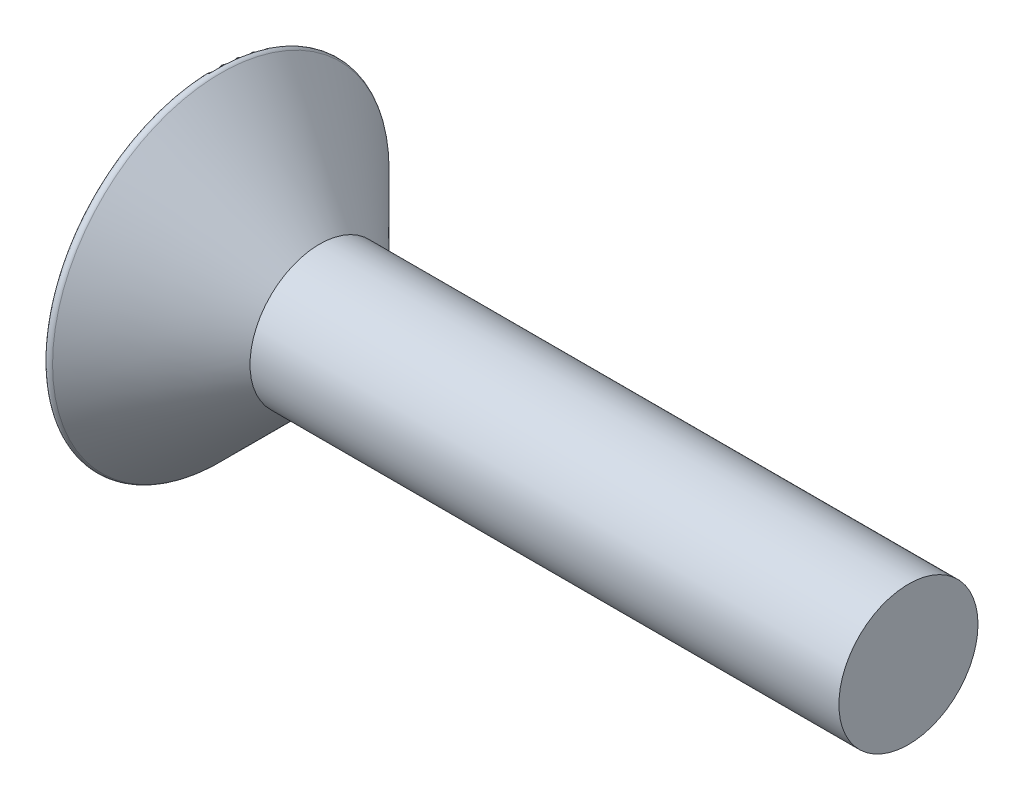
SolidWorks part; units mm, degrees
ref_plane "Front" through (0, 0, 0) normal (0, 0, 1) x (1, 0, 0)
ref_plane "Top" through (0, 0, 0) normal (0, 1, 0) x (1, 0, 0)
ref_plane "Right" through (0, 0, 0) normal (1, 0, 0) x (0, 0, -1)
ref_plane "Plane1" through (4.6, 0, 0) normal (1, 0, 0) x (0, 0, -1)
sketch "Sketch1" plane through (4.6, 0, 0) normal (1, 0, 0) x (0, 0, -1)
  circle A0 centre (0, 0) radius 3
  dimension "d" = 6
extrude "BaseHead" add sketch "Sketch1" against normal blind 4.6 draft 45 draft outward yes
sketch "Sketch2" plane through (4.6, 0, 0) normal (1, 0, 0) x (0, 0, -1)
  circle A1 centre (0, 0) radius 3
  dimension "d" = 6
extrude "BaseBody" add sketch "Sketch2" along normal blind 30
cosmetic thread "ThreadCosmetic1" [suppressed] parameters "bb"=23.4, "THD_MINOR"=5
sketch "Sketch7" plane through (0, 0, 0) normal (0, 0, 1) x (1, 0, 0)
  line L0 (30, 6) -> (30, -6)
  line L1 (34.6, -3) -> (34.6, 3) construction
  line L2 (34.6, 3) -> (4.6, 3) construction
  line L3 (4.6, -3) -> (34.6, -3) construction
  dimension "D1" = 4.6
  dimension "D2" = 3
  dimension "D3" = 3
extrude "Cut-Extrude3" cut sketch "Sketch7" against normal through all and the other way through all
sketch "Sketch8" plane through (0, 0, 0) normal (0, 0, 1) x (1, 0, 0)
  line L0 (0, 7.6) -> (4.6, 3)
  line L2 (6.3071, 2.7071) -> (6.6, 3)
  line L3 (6.6, 3) -> (6.6, 7.6)
  line L4 (6.6, 7.6) -> (0, 7.6)
  line L5 (30, 3) -> (4.6, 3) construction
  line L6 (0, 0) -> (8.9995, 0) construction
  line L7 (4.6, 3) -> (4.6, -3) construction
  arc A0 (4.6, 3) -> (6.3071, 2.7071) centre (5.6607, 4.0607) ccw
  dimension "r" = 1.5
  dimension "D1" = 45
  dimension "a" = 2
sketch "Sketch4" plane through (0, 0, 0) normal (1, 0, 0) x (0, 0, -1)
  line L1 (2.396, 0) -> (1.198, 2.075)
  line L2 (1.198, 2.075) -> (-1.198, 2.075)
  line L3 (-1.198, 2.075) -> (-2.396, 0)
  line L4 (-2.396, 0) -> (-1.198, -2.075)
  line L5 (-1.198, -2.075) -> (1.198, -2.075)
  line L6 (1.198, -2.075) -> (2.396, 0)
  circle A0 centre (0, 0) radius 2.075 construction
  dimension "B" = 4.15
extrude "Socket" cut sketch "Sketch4" along normal blind 2
sketch "Sketch5" plane through (2, 0, 0) normal (-1, 0, 0) x (0, 0, 1)
  line L0 (-1.198, 2.075) -> (1.198, 2.075) construction
  line L1 (1.198, 2.075) -> (2.396, 0) construction
  line L2 (2.396, 0) -> (1.198, -2.075) construction
  line L3 (1.198, -2.075) -> (-1.198, -2.075) construction
  line L4 (-2.396, 0) -> (-1.198, 2.075) construction
  line L5 (-1.198, -2.075) -> (-2.396, 0) construction
  line L6 (-1.198, 2.075) -> (1.198, 2.075)
  line L7 (1.198, 2.075) -> (2.396, 0)
  line L8 (2.396, 0) -> (1.198, -2.075)
  line L9 (1.198, -2.075) -> (-1.198, -2.075)
  line L10 (-2.396, 0) -> (-1.198, 2.075)
  line L11 (-1.198, -2.075) -> (-2.396, 0)
extrude "Cut-Extrude2" cut sketch "Sketch5" against normal blind 5 draft 60
sketch "Sketch6" plane through (-30.7487, 13.2487, 0) normal (0, 0, 1) x (0, -1, 0)
  line L0 (13.2487, 89.8637) -> (13.2487, 24.8312) construction
  line L1 (10.6609, 35.7609) -> (10.2487, 35.3487)
  line L2 (-7.1919, 35.3487) -> (-7.1919, 22.7487)
  line L3 (-7.1919, 22.7487) -> (10.2487, 22.7487)
  line L4 (10.7487, 35.973) -> (10.7487, 21.4009)
  line L5 (16.2487, 60.7487) -> (10.2487, 60.7487) construction
  line L6 (10.2487, 22.7487) -> (10.7487, 21.4009)
  line L8 (10.2487, 35.3487) -> (-7.1919, 35.3487)
  arc A0 (10.7487, 35.973) -> (10.6609, 35.7609) centre (10.4487, 35.973) cw
  dimension "D3" = 0.3
  dimension "d1" = 5
  dimension "b" = 38
  dimension "x" = 1.3478
  dimension "d" = 6
fillet "HeadFillet" radius 0.2 1 edges at (0, 0, -7.6)
sketch "Sketch9" plane through (0, 0, 0) normal (0, 0, 1) x (1, 0, 0)
  line L0 (30, 2.567) -> (30.25, 3)
  line L1 (30.25, 3) -> (30.25, 3.5)
  line L2 (30.25, 3.5) -> (29.75, 3.5)
  line L3 (29.75, 3.5) -> (29.75, 3)
  line L4 (29.75, 3) -> (30, 2.567)
  line L5 (0, 0) -> (36.7555, 0) construction
  line L6 (30, -3) -> (30, 3) construction
  dimension "D1" = 6
  dimension "D2" = 0.5
revolve "Cut-Revolve10" [suppressed] cut sketch "Sketch9" angle 360 about L5
pattern_linear "LPattern10" [suppressed] count 39 spacing 0.6 along (-1, 0, 0) of bodies 108
equation "\"D1@Plane1\" = \"k@BaseHead\""
equation "\"D1@Sketch7\" = \"k@BaseHead\""
equation "\"D1@Sketch9\" = \"d@Sketch2\""
equation "\"D2@Sketch9\" =  ( \"d@Sketch2\" - \"THD_MINOR@ThreadCosmetic1\" )  / 2"
equation "\"D3@LPattern10\" = \"D2@Sketch9\" * 1.2"
equation "\"D1@LPattern10\" = \"bb@ThreadCosmetic1\" / \"D3@LPattern10\" "
